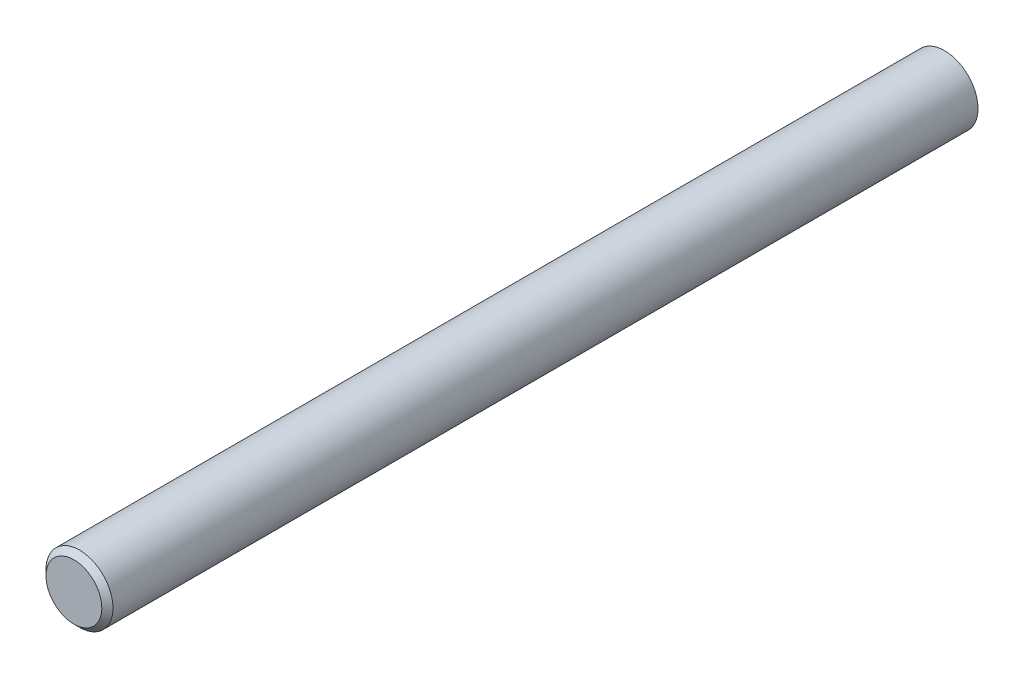
SolidWorks part; units mm, degrees
ref_plane "Ebene vorne" through (0, 0, 0) normal (0, 0, 1) x (1, 0, 0)
ref_plane "Ebene oben" through (0, 0, 0) normal (0, 1, 0) x (1, 0, 0)
ref_plane "Ebene rechts" through (0, 0, 0) normal (1, 0, 0) x (0, 0, -1)
sketch "Skizze1" plane through (0, 0, 0) normal (1, 0, 0) x (0, 0, -1)
  line L0 (7, 3) -> (2, 3) construction
  line L1 (56, 3) -> (56, 0) construction
  line L2 (0, 0) -> (99, 0) construction
  line L3 (7, 3) -> (56, 3) construction
  line L4 (-22, 0) -> (0, 0) construction
  line L5 (-22, 3) -> (-22, 0) construction
  line L6 (2, 3) -> (-22, 3) construction
  line L7 (7, 3) -> (2, 3)
  line L8 (56, 3) -> (56, 0)
  line L9 (0, 0) -> (56, 0)
  line L10 (7, 3) -> (56, 3)
  line L11 (-22, 0) -> (0, 0)
  line L12 (-22, 3) -> (-22, 0)
  line L13 (2, 3) -> (-22, 3)
revolve "Rotation1" add sketch "Skizze1" angle 360 about L11
chamfer "Fase1" distance 0.5 angle 45 1 edges at (0, -3, 22)
